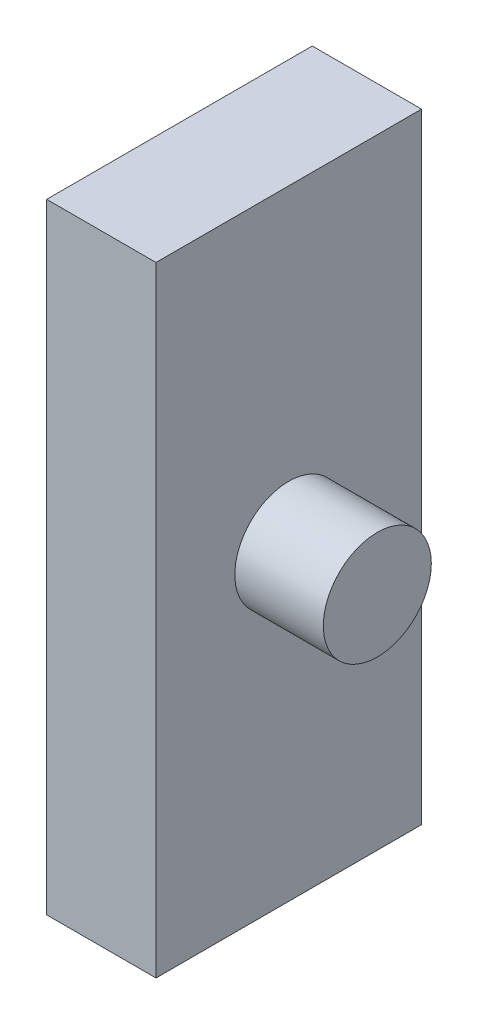
SolidWorks part; units mm, degrees
ref_plane "Front Plane" through (0, 0, 0) normal (0, 0, 1) x (1, 0, 0)
ref_plane "Top Plane" through (0, 0, 0) normal (0, 1, 0) x (1, 0, 0)
ref_plane "Right Plane" through (0, 0, 0) normal (1, 0, 0) x (0, 0, -1)
sketch "Sketch1" plane through (0, 0, 0) normal (1, 0, 0) x (0, 0, -1)
  line L0 (5.8625, 17.5) -> (9.1375, 17.5) construction
  line L1 (5.8625, 24) -> (9.1375, 24)
  line L2 (5.8625, 24) -> (5.8625, 11)
  line L3 (5.8625, 11) -> (9.1375, 11)
  line L4 (9.1375, 24) -> (9.1375, 11)
  line L5 (7.5, 24) -> (7.5, 11) construction
  line L6 (7.5, 35) -> (7.5, 0) construction
  line L15 (0, 35) -> (15, 35)
  line L16 (0, 35) -> (0, 0)
  line L17 (0, 0) -> (15, 0)
  line L18 (15, 35) -> (15, 0)
  line L19 (0, 17.5) -> (15, 17.5) construction
  dimension "D2" = 3.275
  dimension "D3" = 13
  dimension "D4" = 15
  dimension "D5" = 35
extrude "Boss-Extrude1" add sketch "Sketch1" along normal blind 4.175
sketch "Sketch2" plane through (4.175, 0, 0) normal (1, 0, 0) x (0, 0, -1)
  line L1 (0, 35) -> (15, 35)
  line L2 (0, 35) -> (0, 0)
  line L3 (0, 0) -> (15, 0)
  line L4 (15, 35) -> (15, 0)
extrude "Boss-Extrude2" add sketch "Sketch2" along normal blind 2
sketch "Sketch3" plane through (6.175, 0, 0) normal (1, 0, 0) x (0, 0, -1)
  line L0 (7.5, 35) -> (7.5, 0) construction
  line L1 (15, 35) -> (0, 35) construction
  line L2 (0, 0) -> (15, 0) construction
  line L3 (0, 17.5) -> (15, 17.5) construction
  line L4 (0, 35) -> (0, 0) construction
  line L5 (15, 0) -> (15, 35) construction
  circle A0 centre (7.5, 17.5) radius 3.05
  dimension "D1" = 6.1
extrude "Boss-Extrude3" add sketch "Sketch3" along normal blind 5
